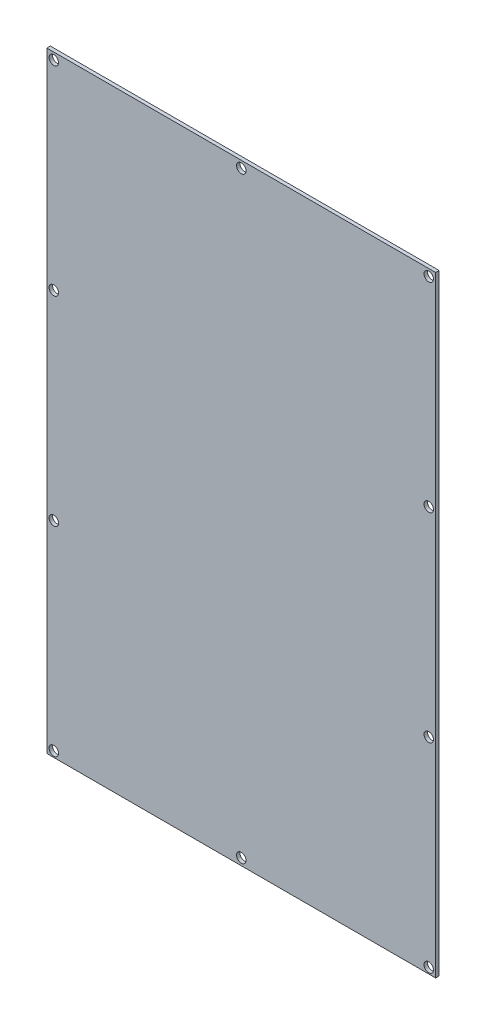
SolidWorks part; units mm, degrees
ref_plane "Front Plane" through (0, 0, 0) normal (0, 0, 1) x (1, 0, 0)
ref_plane "Top Plane" through (0, 0, 0) normal (0, 1, 0) x (1, 0, 0)
ref_plane "Right Plane" through (0, 0, 0) normal (1, 0, 0) x (0, 0, -1)
sketch "Sketch1" plane through (0, 0, 0) normal (0, 0, 1) x (1, 0, 0)
  line L1 (0, 0) -> (177.8, 0)
  line L2 (0, 0) -> (0, 279.4)
  line L3 (0, 279.4) -> (177.8, 279.4)
  line L4 (177.8, 0) -> (177.8, 279.4)
  dimension "D1" = 279.4
  dimension "D2" = 177.8
extrude "Boss-Extrude1" add sketch "Sketch1" along normal blind 1.5875
sketch "Sketch2" plane through (0, 0, 1.5875) normal (0, 0, 1) x (1, 0, 0)
  line L24 (3.175, 3.175) -> (174.625, 3.175)
  line L25 (174.625, 3.175) -> (174.625, 276.225)
  line L26 (3.175, 276.225) -> (3.175, 3.175)
  line L27 (174.625, 276.225) -> (3.175, 276.225)
  line L28 (3.175, 3.175) -> (174.625, 3.175) construction
  line L29 (174.625, 3.175) -> (174.625, 276.225) construction
  line L30 (3.175, 276.225) -> (3.175, 3.175) construction
  line L31 (174.625, 276.225) -> (3.175, 276.225) construction
  circle A0 centre (3.175, 276.225) radius 2.159
  circle A1 centre (88.9, 276.225) radius 2.159
  circle A2 centre (174.625, 276.225) radius 2.159
  circle A3 centre (3.175, 185.039) radius 2.159
  circle A4 centre (174.625, 185.039) radius 2.159
  circle A5 centre (3.175, 93.853) radius 2.159
  circle A6 centre (174.625, 93.853) radius 2.159
  circle A7 centre (3.175, 2.667) radius 2.159
  circle A8 centre (174.625, 2.667) radius 2.159
  circle A9 centre (88.9, 3.175) radius 2.159
  dimension "D2" = 4.318
  dimension "D1" = 3.175
  dimension "D3" = 4
extrude "Cut-Extrude1" cut sketch "Sketch2" against normal through all
